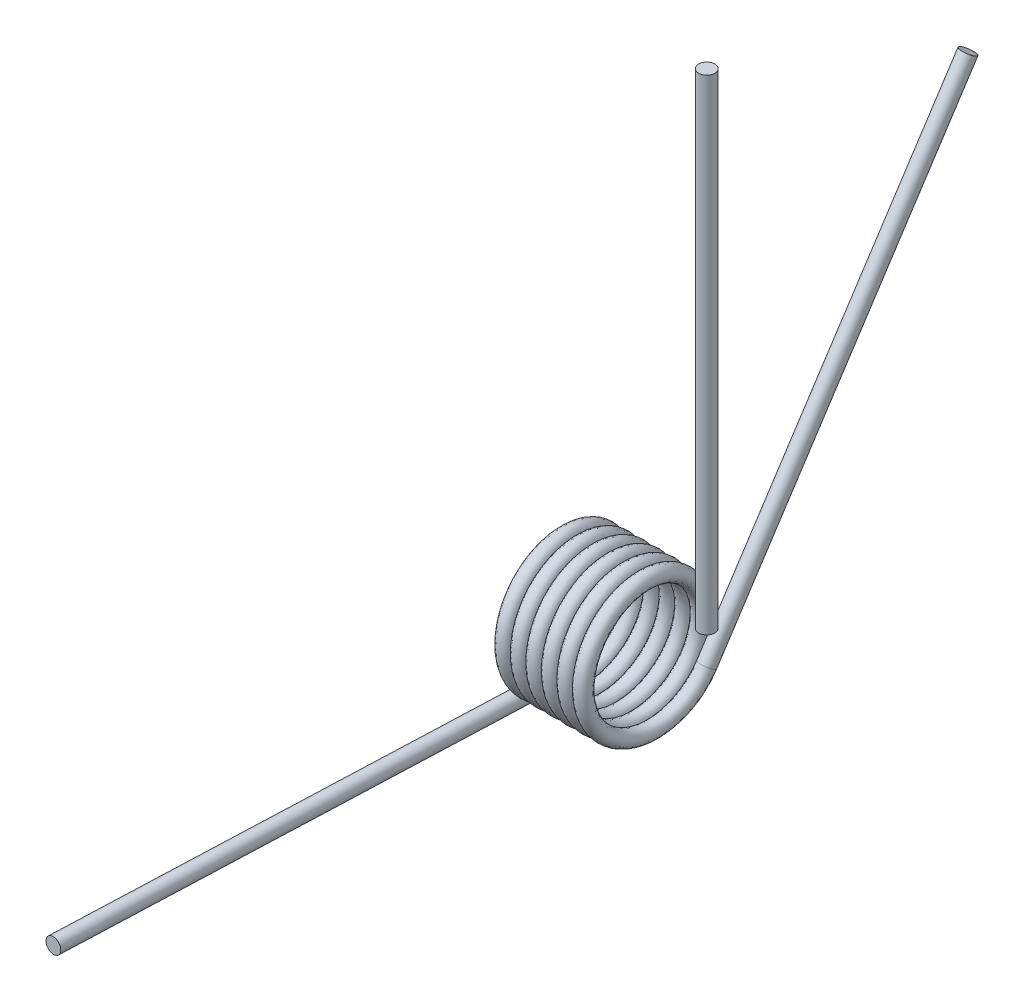
SolidWorks part; units mm, degrees
ref_plane "Front" through (0, 0, 0) normal (0, 0, 1) x (1, 0, 0)
ref_plane "Top" through (0, 0, 0) normal (0, 1, 0) x (1, 0, 0)
ref_plane "Right" through (0, 0, 0) normal (1, 0, 0) x (0, 0, -1)
sketch "Sketch1" plane through (0, 0, 0) normal (1, 0, 0) x (0, 0, -1)
  line L0 (0, -8.6487) -> (0, -11.0617) construction
  line L1 (9.5797, -5.5309) -> (47.6797, 60.4603) construction
  line L2 (0, -11.0617) -> (-76.2, -11.0617) construction
  line L3 (0, 0) -> (11.0617, 0) construction
  line L4 (0, 0) -> (9.5797, -5.5309) construction
  line L5 (-76.2, -11.0617) -> (-76.2, -8.6487) construction
  line L6 (-76.2, -8.6487) -> (0, -8.6487) construction
  line L7 (47.6797, 60.4603) -> (45.59, 61.6668) construction
  line L8 (45.59, 61.6668) -> (7.49, -4.3244) construction
  circle A0 centre (0, 0) radius 11.0617 construction
  circle A1 centre (0, 0) radius 7.9375 construction
  circle A2 centre (0, 0) radius 9.8552 construction
  point P7 (0, -9.8552)
  point P10 (0, 11.0617)
  dimension "OD" = 22.1234
  dimension "For Shaft Diameter" = 15.875
  dimension "Wire Diameter" = 2.413
  dimension "Leg Length" = 76.2
  dimension "Deflection Angle" = 120
sketch "Sketch2" plane through (0, 0, 0) normal (1, 0, 0) x (0, 0, -1)
  circle A0 centre (0, 0) radius 9.8552 construction
  circle A2 centre (0, 0) radius 9.8552
curve "Helix/Spiral1" pitch 2.4384 height 15.0368 radius 9.8552 centre (0, 0, 0) axis (1, 0, 0) start towards (0, 0, -1)
ref_plane "Plane1" through (0, -9.8552, 0) normal (0.0393, 0, -0.9992) x (0.999, -0.0232, 0.0393)
sketch "Sketch3" plane through (0, -9.8552, 0) normal (0.0393, 0, -0.9992) x (0.999, -0.0232, 0.0393)
  circle A0 centre (0, 0) radius 1.2065
  dimension "D1" = 2.413
sweep "Sweep1" add profiles "Sketch3" path "Helix/Spiral1"
sketch "Sketch4" plane through (0, 0, 0) normal (-0.0393, 0, 0.9992) x (-0.999, 0.0232, -0.0393)
  circle A1 centre (-0.229, 9.8525) radius 1.2065
  circle A2 centre (-0.229, 9.8525) radius 1.2065
  dimension "D1" = 0
extrude "Extrude1" add sketch "Sketch4" along normal blind 76.2
sketch "Sketch5" plane through (0.0233, 0.512, -0.2956) normal (0.0393, 0.8654, -0.4996) x (0.9982, -0.0569, -0.02)
  circle A1 centre (15.4605, 9.1571) radius 1.2065
  circle A2 centre (15.4605, 9.1571) radius 1.2065
  dimension "D1" = 0
extrude "Extrude2" add sketch "Sketch5" along normal blind 76.2
sketch "Sketch6" plane through (0, 0, 0) normal (1, 0, 0) x (0, 0, -1)
  circle A2 centre (0, 0) radius 8.6487 construction
sketch "Sketch7" plane through (0, 0, 0) normal (0, 1, 0) x (1, 0, 0)
  circle A0 centre (15.0368, 8.5349) radius 1.27
  ellipse E0 centre (15.0368, 8.5349) end of major axis (13.834, 8.6296) minor radius 1.0441 construction
  dimension "D1" = 2.54
extrude "Boss-Extrude1" add sketch "Sketch7" along normal blind 76.2
sketch "Sketch8" plane through (0, 0, 0) normal (1, 0, 0) x (0, 0, -1)
  line L0 (0, 0) -> (-69.683, 0)
  circle A0 centre (0, 0) radius 17.4684
equation "\"D4@Helix/Spiral1\" = \"Wire Diameter@Sketch1\" + .001"
equation "\"D1@Sketch3\"=\"Wire Diameter@Sketch1\""
equation "\"D1@Extrude2\"=\"Leg Length@Sketch1\""
equation "\"Leg Length@Extrude1\"=\"Leg Length@Sketch1\""
